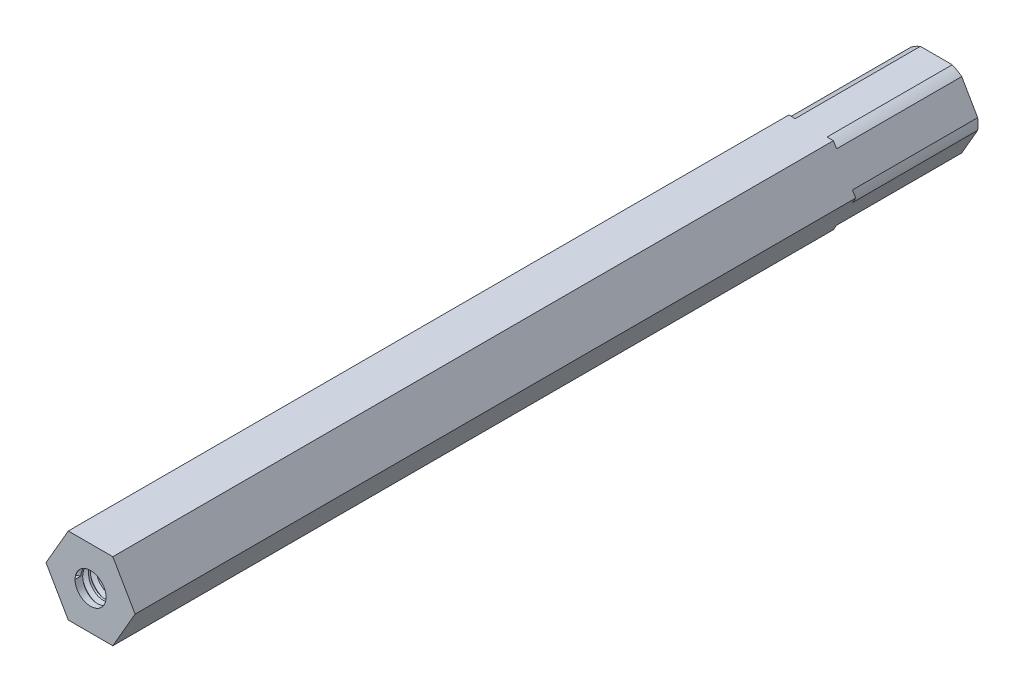
SolidWorks part; units mm, degrees
material "7075-T6 (SN)"
ref_plane "Alzado" through (0, 0, 0) normal (0, 0, 1) x (1, 0, 0)
ref_plane "Planta" through (0, 0, 0) normal (0, 1, 0) x (1, 0, 0)
ref_plane "Vista lateral" through (0, 0, 0) normal (1, 0, 0) x (0, 0, -1)
sketch "Croquis2" plane through (0, 0, 0) normal (0, 0, 1) x (1, 0, 0)
  line L1 (3.6662, -6.35) -> (7.3323, 0)
  line L2 (7.3323, 0) -> (3.6662, 6.35)
  line L3 (3.6662, 6.35) -> (-3.6662, 6.35)
  line L4 (-3.6662, 6.35) -> (-7.3323, 0)
  line L5 (-7.3323, 0) -> (-3.6662, -6.35)
  line L6 (-3.6662, -6.35) -> (3.6662, -6.35)
  circle A0 centre (0, 0) radius 6.35 construction
  dimension "D1" = 12.7
extrude "Extrusión Hex Profile" add sketch "Croquis2" along normal mid plane 139.192
sketch "Croquis3" plane through (0, 0, 0) normal (0, 0, 1) x (1, 0, 0)
  circle A0 centre (0, 0) radius 2.5527
  dimension "D1" = 5.1054
extrude "Tap Hole 1" cut sketch "Croquis3" against normal blind 19.05 from surface starting at face at (0, 0, 69.596)
extrude "Tap Hole 2" cut sketch "Croquis3<3>" along normal blind 19.05 from surface starting at face at (0, 0, -69.596)
sketch "Croquis3<3>" plane through (0, 0, 0) normal (0, 0, 1) x (1, 0, 0) same geometry as "Croquis3"
sketch "Croquis7" plane through (0, 0, 0) normal (0, 0, 1) x (1, 0, 0)
  circle A0 centre (0, 0) radius 6.8707
  dimension "D1" = 13.7414
extrude "ThunderHex" cut sketch "Croquis7" along normal blind 20.5994 from surface flip side to cut starting at face at (2.5527, 0, -69.596)
sketch "Croquis8" plane through (0, 0, 0) normal (0, 1, 0) x (1, 0, 0)
  line L0 (0, -69.596) -> (-5.5562, -69.596) construction
  line L1 (3.6662, -69.596) -> (-3.6662, -69.596) construction
  line L3 (0, -69.596) -> (0, 0) construction
  line L4 (-5.5562, -69.596) -> (-6.35, -68.8023)
  line L5 (-6.35, -68.8023) -> (-6.35, -68.0085)
  line L6 (-6.35, -68.0085) -> (-5.9055, -68.0085)
  line L7 (-5.9055, -68.0085) -> (-5.9055, -66.421)
  line L8 (-5.9055, -66.421) -> (-12.7, -66.421)
  line L9 (-12.7, -66.421) -> (-12.7, -69.596)
  line L10 (-12.7, -69.596) -> (-5.5562, -69.596)
  line L11 (-3.6662, -69.596) -> (-7.3323, -69.596) construction
  dimension "D1" = 11.811
  dimension "D2" = 12.7
  dimension "D3" = 45
  dimension "D4" = 0.7937
  dimension "D6" = 0.7937
  dimension "D7" = 3.175
  dimension "D8" = 25.4
revolve "Retaining Ring 1" [suppressed] cut sketch "Croquis8" angle 360 about L3
sketch "Croquis9" plane through (0, 0, 0) normal (0, -1, 0) x (1, 0, 0)
  line L0 (0, -69.596) -> (-5.5562, -69.596) construction
  line L3 (0, -69.596) -> (0, 0) construction
  line L4 (-5.5562, -69.596) -> (-6.35, -68.8023)
  line L5 (-6.35, -68.8023) -> (-6.35, -68.0085)
  line L6 (-6.35, -68.0085) -> (-5.9055, -68.0085)
  line L7 (-5.9055, -68.0085) -> (-5.9055, -66.421)
  line L8 (-5.9055, -66.421) -> (-12.7, -66.421)
  line L9 (-12.7, -66.421) -> (-12.7, -69.596)
  line L10 (-12.7, -69.596) -> (-5.5562, -69.596)
  line L12 (-2.6237, -69.596) -> (2.6237, -69.596) construction
  line L13 (-6.8111, -69.596) -> (-4.1874, -69.596) construction
  dimension "D1" = 11.811
  dimension "D2" = 12.7
  dimension "D3" = 45
  dimension "D4" = 0.7937
  dimension "D6" = 0.7937
  dimension "D7" = 3.175
  dimension "D8" = 25.4
revolve "Retaining Ring 2" [suppressed] cut sketch "Croquis9" angle 360 about L3
sketch "Croquis10" plane through (0, 0, 0) normal (0, 1, 0) x (1, 0, 0)
  line L0 (0, -69.596) -> (0, 0) construction
  line L1 (3.6662, -69.596) -> (-3.6662, -69.596) construction
  line L2 (0, -69.596) -> (-5.5562, -69.596) construction
  line L3 (-3.6662, -69.596) -> (-7.3323, -69.596) construction
  line L4 (-5.5562, -69.596) -> (-6.35, -68.8023)
  line L5 (-6.35, -68.8023) -> (-6.35, -61.6458)
  line L6 (-6.35, -61.6458) -> (-9.525, -61.6458)
  line L7 (-9.525, -61.6458) -> (-9.525, -69.596)
  line L8 (-9.525, -69.596) -> (-5.5562, -69.596)
  dimension "D2" = 12.7
  dimension "D1" = 45
  dimension "D3" = 0.7937
  dimension "D4" = 7.9502
  dimension "D5" = 19.05
revolve "Round End 1" [suppressed] cut sketch "Croquis10" angle 360 about L0
sketch "Croquis12" plane through (0, 0, 0) normal (0, -1, 0) x (1, 0, 0)
  line L0 (0, -69.596) -> (0, 0) construction
  line L2 (0, -69.596) -> (-5.5562, -69.596) construction
  line L4 (-5.5562, -69.596) -> (-6.35, -68.8023)
  line L5 (-6.35, -68.8023) -> (-6.35, -61.6458)
  line L6 (-6.35, -61.6458) -> (-9.525, -61.6458)
  line L7 (-9.525, -61.6458) -> (-9.525, -69.596)
  line L8 (-9.525, -69.596) -> (-5.5562, -69.596)
  line L9 (-2.6237, -69.596) -> (2.6237, -69.596) construction
  dimension "D1" = 45
  dimension "D3" = 0.7937
  dimension "D4" = 7.9502
  dimension "D2" = 12.7
  dimension "D5" = 19.05
revolve "Round End 2" [suppressed] cut sketch "Croquis12" angle 360 about L0
thread "Rosca1" pitch 1.27 method cut profile "Perfil de rosca1" start angle 0, offset 0, length 0, pitch 1.27, diameter 5.1054
ref_plane "Plano1" through (-2.5527, 0, 69.596) normal (0, -1, 0) x (-1, 0, 0)
sketch "Perfil de rosca1" plane through (-2.5527, 0, 69.596) normal (0, -1, 0) x (-1, 0, 0)
  line L0 (0, 0) -> (0, 1.27) construction
  line L1 (0, 0) -> (0.6874, 0.3969)
  line L2 (0.6874, 0.3969) -> (0.6874, 0.5556)
  line L3 (0.6874, 0.5556) -> (0, 0.9525)
  line L4 (0.6874, 0.4762) -> (0, 0.4762) construction
  line L11 (0, 0) -> (0, 0.9525)
  point P2 (0, 0)
  dimension "Pitch" = 1.27
  dimension "Profile_Angle" = 60
  dimension "Profile_Land" = 0.1588
  dimension "Profile_Height" = 0.6874
thread "Rosca2" pitch 1.27 method cut profile "Perfil de rosca2" start angle 0, offset 0, length 0, pitch 1.27, diameter 5.1054
ref_plane "Plano2" through (2.5527, 0, -69.596) normal (0, -1, 0) x (1, 0, 0)
sketch "Perfil de rosca2" plane through (2.5527, 0, -69.596) normal (0, -1, 0) x (1, 0, 0)
  line L0 (0, 0) -> (0, 1.27) construction
  line L1 (0, 0) -> (0.6874, 0.3969)
  line L2 (0.6874, 0.3969) -> (0.6874, 0.5556)
  line L3 (0.6874, 0.5556) -> (0, 0.9525)
  line L4 (0.6874, 0.4762) -> (0, 0.4762) construction
  line L11 (0, 0) -> (0, 0.9525)
  point P2 (0, 0)
  dimension "Pitch" = 1.27
  dimension "Profile_Angle" = 60
  dimension "Profile_Land" = 0.1588
  dimension "Profile_Height" = 0.6874
equation "\"HexOD\"= 0.5pulgadas"
equation "\"Largo\"= 5.48pulgadas"
equation "\"D1@Croquis2\"=\"HexOD\""
equation "\"D1@Extrusión Hex Profile\" = \"Largo\""
equation "\"TapHole\"= IIF ( \"HexOD\" = 0.5pulgadas , 0.2010pulgadas , 0.190pulgadas )"
equation "\"D1@Croquis3\"=\"TapHole\""
equation "\"ProTapHole\"= 0.75pulgadas"
equation "\"D1@Tap Hole 1\" = \"ProTapHole\""
equation "\"D1@Tap Hole 2\" = \"ProTapHole\""
equation "\"ThunderHex\"= IIF ( \"HexOD\" = 0.5pulgadas , 0.541pulgadas , 0.4035pulgadas )"
equation "\"D1@Croquis7\"=\"ThunderHex\""
equation "\"D2@Croquis8\"=\"HexOD\""
equation "\"D1@Croquis8\"=if(\"HexOD\"=0.5pulgadas, 0.465pulgadas, 0.35pulgadas )"
equation "\"D2@Croquis9\"=\"HexOD\""
equation "\"D1@Croquis9\"=if(\"HexOD\"=0.5pulgadas, 0.465pulgadas, 0.35pulgadas )"
equation "\"D8@Croquis8\"=\"HexOD\"*2"
equation "\"D8@Croquis9\"=\"HexOD\"*2"
equation "\"D5@Croquis10\"=\"HexOD\"*1.5"
equation "\"D5@Croquis12\"=\"HexOD\"*1.5"
equation "\"D4@Croquis10\"=if( \"D2@Croquis10\"=<0.375, 0.28, 0.313)"
equation "\"D4@Croquis12\"=if( \"D2@Croquis10\"=<0.375, 0.28, 0.313)"
